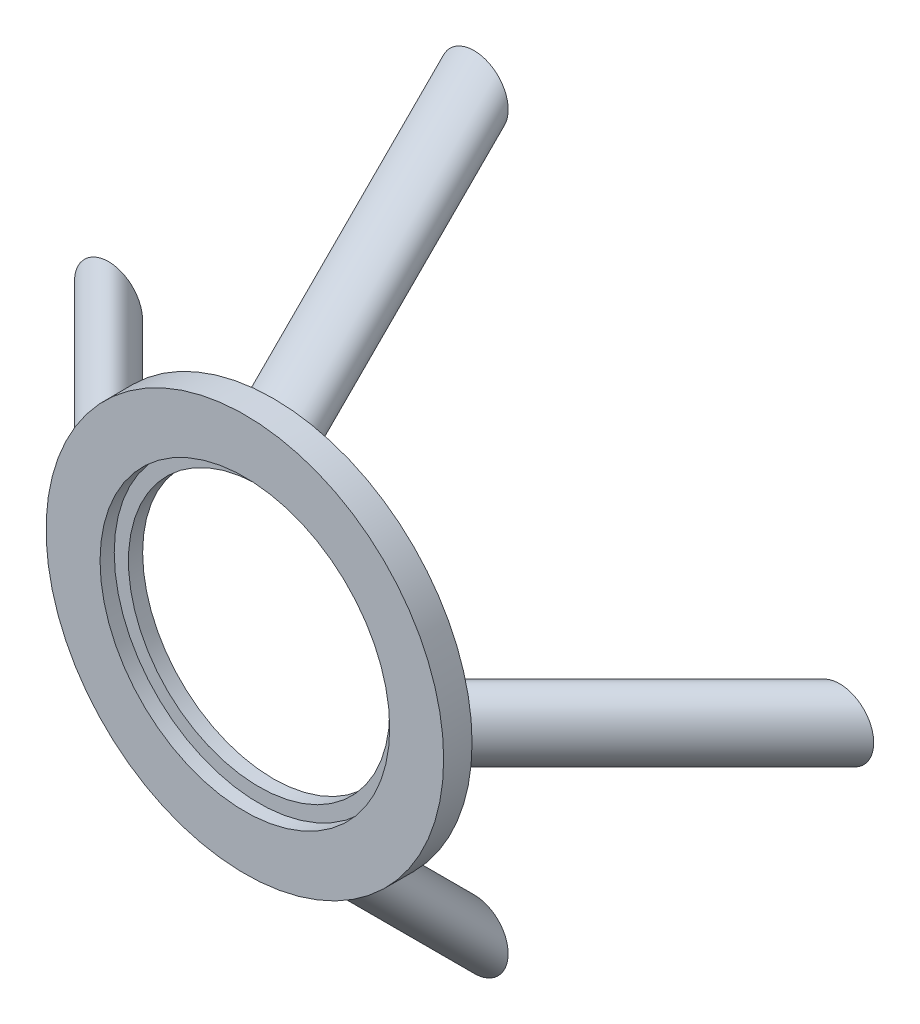
SolidWorks part; units mm, degrees
ref_plane "Front Plane" through (0, 0, 0) normal (0, 0, 1) x (1, 0, 0)
ref_plane "Top Plane" through (0, 0, 0) normal (0, 1, 0) x (1, 0, 0)
ref_plane "Right Plane" through (0, 0, 0) normal (1, 0, 0) x (0, 0, -1)
sketch "Sketch1" plane through (0, 0, 0) normal (0, 0, 1) x (1, 0, 0)
  circle A1 centre (0, 0) radius 70
  circle A2 centre (0, 0) radius 51
  circle A3 centre (0, 0) radius 46
  dimension "D1" = 5
extrude "Boss-Extrude1" add sketch "Sketch1" along normal blind 10 contours A2 | A1
extrude "Boss-Extrude3" add sketch "Sketch1<6>" along normal blind 5 contours A2 A3 region at (-49.5575, 0, 0)
sketch "Sketch1<6>" plane through (0, 0, 0) normal (0, 0, 1) x (1, 0, 0) same geometry as "Sketch1"
sketch "Sketch2" plane through (0, 0, 0) normal (0, 0, -1) x (-1, 0, 0)
  circle A0 centre (0, -58) radius 12
  circle A1 centre (0, 0) radius 70 construction
  circle A2 centre (0, 0) radius 46 construction
sketch "Sketch3" plane through (0, 0, 0) normal (1, 0, 0) x (0, 0, -1)
  line L0 (0, -58) -> (70.7107, -128.7107)
  line L1 (0, -70) -> (0, -46) construction
sweep "Sweep1" add profiles "Sketch2" path "Sketch3"
sketch "Sketch4" plane through (0, 0, 0) normal (0, 0, -1) x (-1, 0, 0)
  circle A0 centre (0, 0) radius 46
pattern_circular "CirPattern2" count 4 over 360 about axis through (0, 0, 10) along (0, 0, -1) of "Sweep1"
